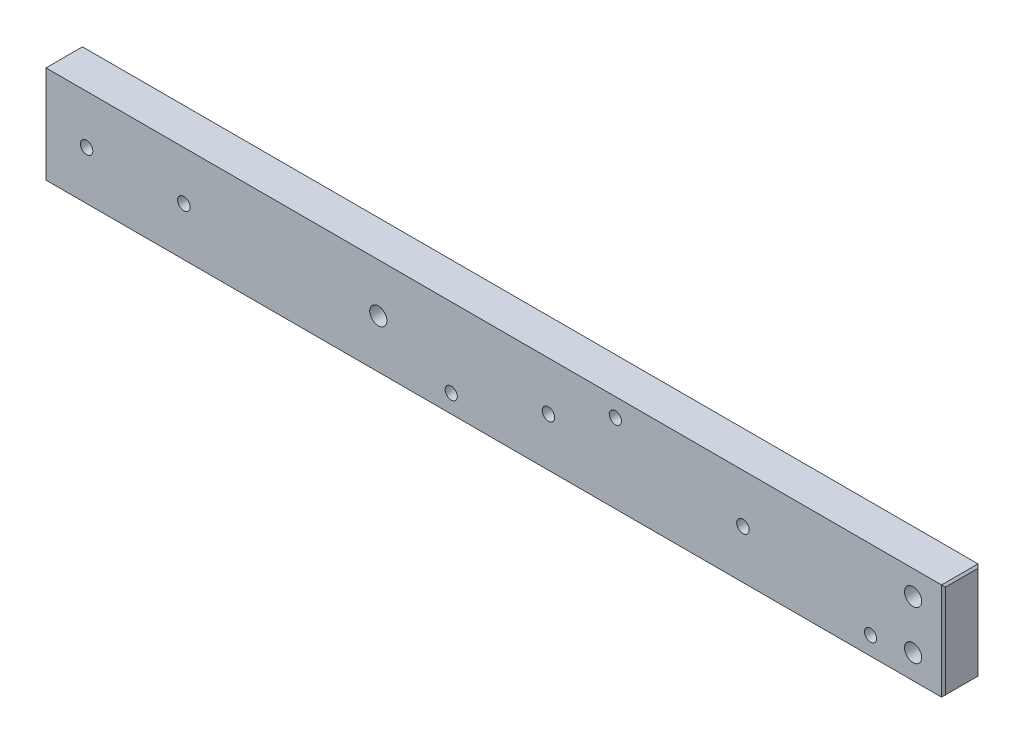
SolidWorks part; units mm, degrees
material "6061-T6 (SS)"
ref_plane "Front Plane" through (0, 0, 0) normal (0, 0, 1) x (1, 0, 0)
ref_plane "Top Plane" through (0, 0, 0) normal (0, 1, 0) x (1, 0, 0)
ref_plane "Right Plane" through (0, 0, 0) normal (1, 0, 0) x (0, 0, -1)
sketch "Sketch1" plane through (0, 0, 0) normal (0, 0, 1) x (1, 0, 0)
  line L1 (0, 0) -> (-234.95, 0)
  line L2 (0, 0) -> (0, 25.4)
  line L3 (0, 25.4) -> (-234.95, 25.4)
  line L4 (-234.95, 0) -> (-234.95, 25.4)
  dimension "D1" = 25.4
  dimension "D2" = 234.95
extrude "Boss-Extrude1" add sketch "Sketch1" along normal blind 9.525
sketch "Sketch2" plane through (0, 0, 9.525) normal (0, 0, 1) x (1, 0, 0)
  line L0 (-7.9375, 6.35) -> (-7.9375, 19.05)
  line L1 (-7.9375, 19.05) -> (-7.9375, 25.4)
  line L2 (0, 25.4) -> (-234.95, 25.4) construction
  line L3 (-7.9375, 6.35) -> (-7.9375, 0)
  line L4 (-234.95, 0) -> (0, 0) construction
  line L5 (0, 0) -> (0, 25.4) construction
  dimension "D1" = 7.9375
  dimension "D2" = 12.7
hole_wizard "#8 Clearance Hole1" positions "Sketch3" profile "Sketch4" hole size "#8" standard "ANSI Inch"
sketch "Sketch3" plane through (0, 0, 9.525) normal (0, 0, 1) x (1, 0, 0)
  point P0 (-7.9375, 6.35)
  point P3 (-7.9375, 19.05)
sketch "Sketch4" plane through (-7.9375, 6.35, 9.525) normal (1, 0, 0) x (0, -1, 0)
  line L0 (0, 0) -> (0, 26.7507)
  line L1 (0, 26.7507) -> (2.2479, 25.4)
  line L2 (2.2479, 25.4) -> (2.2479, 0)
  line L5 (2.2479, 0) -> (0, 0)
  line L10 (0, 26.7507) -> (-2.2479, 25.4) construction
  line L11 (0, -6.35) -> (0, 107.95) construction
  dimension "Hole Dia." = 4.4958
  dimension "Hole Depth" = 25.4
  dimension "Drill Angle" = 118
hole_wizard "#8 Clearance Hole2" positions "Sketch8" profile "Sketch9" hole size "#8" standard "ANSI Inch"
sketch "Sketch8" plane through (0, 0, 9.525) normal (0, 0, 1) x (1, 0, 0)
  line L0 (-211.1375, 12.7) -> (-147.6375, 12.7)
  line L1 (-211.1375, 12.7) -> (-234.95, 12.7)
  line L2 (-234.95, 25.4) -> (-234.95, 0) construction
  point P2 (-147.6375, 12.7)
  dimension "D1" = 63.5
  dimension "D2" = 23.8125
sketch "Sketch9" plane through (-147.6375, 12.7, 9.525) normal (1, 0, 0) x (0, -1, 0)
  line L0 (0, 0) -> (0, 20.4007)
  line L1 (0, 20.4007) -> (2.2479, 19.05)
  line L2 (2.2479, 19.05) -> (2.2479, 0)
  line L5 (2.2479, 0) -> (0, 0)
  line L10 (0, 20.4007) -> (-2.2479, 19.05) construction
  line L11 (0, -6.35) -> (0, 107.95) construction
  dimension "Hole Dia." = 4.4958
  dimension "Hole Depth" = 19.05
  dimension "Drill Angle" = 118
chamfer "Chamfer1" distance 0.508 angle 45 8 edges at (0, 0, 4.7625) (0, 12.7, 9.525) (0, 25.4, 4.7625) (0, 12.7, 0) (-234.95, 25.4, 4.7625) (-234.95, 12.7, 9.525) (-234.95, 0, 4.7625) (-234.95, 12.7, 0)
hole_wizard "#4 Clearance Hole3" positions "Sketch10" profile "Sketch12" hole size "#4" standard "ANSI Inch" end condition through all
sketch "Sketch10" plane through (0, 0, 0) normal (0, 0, -1) x (-1, 0, 0)
  circle A0 centre (52.3875, 12.7) radius 1.1303 construction
  circle A1 centre (52.3875, 12.7) radius 1.1303
  circle A2 centre (103.1875, 12.7) radius 1.1303 construction
  circle A3 centre (103.1875, 12.7) radius 1.1303
  point P0 (103.1875, 12.7)
  point P3 (52.3875, 12.7)
  point P12 (103.1875, 12.7)
  point P13 (52.3875, 12.7)
sketch "Sketch12" plane through (-103.1875, 12.7, 0) normal (1, 0, 0) x (0, 1, 0)
  line L0 (0, 0) -> (0, 9.525)
  line L1 (0, 9.525) -> (1.6319, 9.525)
  line L2 (1.6319, 9.525) -> (1.6319, 0)
  line L5 (1.6319, 0) -> (0, 0)
  line L11 (0, -6.35) -> (0, 107.95) construction
  dimension "Thru Hole Dia." = 3.2639
  dimension "Thru Hole Depth" = 9.525
hole_wizard "#4 Clearance Hole2" positions "Sketch13" profile "Sketch14" hole size "#4" standard "ANSI Inch" end condition up to next
sketch "Sketch13" plane through (0, 0, 9.525) normal (0, 0, 1) x (1, 0, 0)
  line L0 (-223.8375, 12.7) -> (-198.4375, 12.7)
  line L2 (-234.442, 25.4) -> (-234.442, 0) construction
  line L3 (-147.6375, 12.7) -> (-211.1375, 12.7) construction
  point P0 (-223.8375, 12.7)
  point P2 (-198.4375, 12.7)
  point P11 (-234.442, 12.7)
  dimension "D1" = 25.4
  dimension "D2" = 63.5
sketch "Sketch14" plane through (-223.8375, 12.7, 9.525) normal (1, 0, 0) x (0, -1, 0)
  line L0 (0, 0) -> (0, 9.525)
  line L1 (0, 9.525) -> (1.6319, 9.525)
  line L2 (1.6319, 9.525) -> (1.6319, 0)
  line L5 (1.6319, 0) -> (0, 0)
  line L11 (0, -6.35) -> (0, 107.95) construction
  dimension "Thru Hole Dia." = 3.2639
  dimension "Thru Hole Depth" = 9.525
hole_wizard "1/8 (0.125) Diameter Hole1" positions "Sketch15" profile "Sketch17" hole size "1/8" standard "ANSI Inch" end condition up to next
sketch "Sketch15" plane through (0, 0, 9.525) normal (0, 0, 1) x (1, 0, 0)
  line L1 (0, 24.892) -> (0, 0.508) construction
  line L2 (-85.725, 20.6375) -> (-19.05, 4.7625)
  line L6 (-234.442, 0) -> (-0.508, 0) construction
  line L7 (-234.442, 0) -> (-0.508, 0) construction
  line L8 (-0.508, 25.4) -> (-234.442, 25.4) construction
  line L10 (-134.9375, 0) -> (-134.9375, 25.4) construction
  point P0 (-19.05, 4.7625)
  point P2 (-85.725, 20.6375)
  point P22 (-128.5875, 4.7625)
  dimension "D1" = 85.725
  dimension "D2" = 19.05
  dimension "D3" = 4.7625
  dimension "D4" = 4.7625
  dimension "D5" = 6.35
  dimension "D6" = 4.7625
sketch "Sketch17" plane through (-19.05, 4.7625, 9.525) normal (1, 0, 0) x (0, -1, 0)
  line L0 (0, 0) -> (0, 9.525)
  line L1 (0, 9.525) -> (1.5875, 9.525)
  line L2 (1.5875, 9.525) -> (1.5875, 0)
  line L5 (1.5875, 0) -> (0, 0)
  line L11 (0, -6.35) -> (0, 107.95) construction
  dimension "Thru Hole Dia." = 3.175
  dimension "Thru Hole Depth" = 9.525
